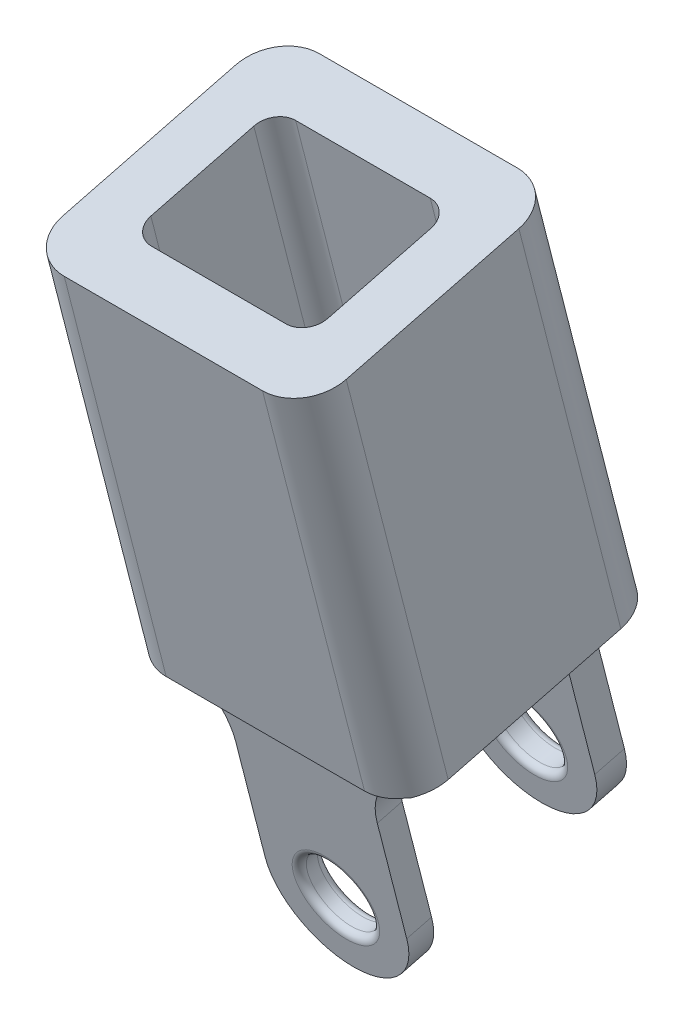
SolidWorks part; units mm, degrees
material "ABS"
ref_plane "Alzado" through (0, 0, 0) normal (0, 0, 1) x (1, 0, 0)
ref_plane "Planta" through (0, 0, 0) normal (0, 1, 0) x (1, 0, 0)
ref_plane "Vista lateral" through (0, 0, 0) normal (1, 0, 0) x (0, 0, -1)
sketch "Croquis1" plane through (0, 0, 0) normal (1, 0, 0) x (0, 0, -1)
  line L0 (268.1146, 425.6206) -> (162.8718, 393.6212) construction
  dimension "D1" = 110
sketch "Croquis2" plane through (0, 0, 0) normal (1, 0, 0) x (0, 0, -1)
  line L0 (116.0336, 334.5851) -> (134.0345, 339.2007)
  line L1 (134.0345, 339.2007) -> (141.2314, 311.1325)
  line L2 (141.2314, 311.1325) -> (123.2306, 306.5169)
  line L3 (123.2306, 306.5169) -> (116.0336, 334.5851)
  line L4 (124.8932, 306.9432) -> (129.4545, 289.1541)
  line L5 (129.4545, 289.1541) -> (144.8187, 293.0936)
  line L6 (144.8187, 293.0936) -> (140.2574, 310.8827)
  line L7 (126.9663, 306.1376) -> (129.9513, 294.496)
  line L8 (129.9513, 294.496) -> (141.4729, 297.4503)
  line L9 (141.4729, 297.4503) -> (138.4879, 309.0918)
  line L10 (138.4879, 309.0918) -> (126.9663, 306.1376)
extrude "Saliente-Extruir1" add sketch "Croquis2" along normal blind 20 contours L3 L2 L1 L0 | L5 L6 L2 L4 L10 L9 L8 L7 region at (0, 322.8588, -128.6325) region at (0, 308.6274, -132.6485)
sketch "Croquis3" plane through (20, 0, 0) normal (1, 0, 0) x (0, 0, -1)
  line L0 (124.8932, 306.9432) -> (140.2574, 310.8827)
  line L1 (124.8932, 306.9432) -> (129.4545, 289.1541)
  line L2 (129.4545, 289.1541) -> (144.8187, 293.0936)
  line L3 (144.8187, 293.0936) -> (140.2574, 310.8827)
extrude "Cortar-Extruir1" cut sketch "Croquis3" against normal blind 5
sketch "Croquis4" plane through (0, 0, 0) normal (-1, 0, 0) x (0, 0, 1)
  line L0 (-144.8187, 293.0936) -> (-140.2574, 310.8827)
  line L1 (-140.2574, 310.8827) -> (-124.8932, 306.9432)
  line L2 (-124.8932, 306.9432) -> (-129.4545, 289.1541)
  line L3 (-129.4545, 289.1541) -> (-144.8187, 293.0936)
extrude "Cortar-Extruir2" cut sketch "Croquis4" against normal blind 5
sketch "Croquis10" plane through (15, 0, 0) normal (1, 0, 0) x (0, 0, -1)
  line L0 (129.9513, 294.496) -> (131.2059, 289.6032)
  line L1 (129.4545, 289.1541) -> (144.8187, 293.0936) construction
  line L2 (129.9513, 294.496) -> (141.4729, 297.4503)
  line L3 (141.4729, 297.4503) -> (142.7274, 292.5574)
  line L4 (142.7274, 292.5574) -> (131.2059, 289.6032)
  line L5 (126.9663, 306.1376) -> (129.9513, 294.496) construction
extrude "Cortar-Extruir4" cut sketch "Croquis10" against normal through all
fillet "Redondeo2" radius 5 6 edges at (5, 289.3786, -130.3302) (15, 289.3786, -130.3302) (15, 292.8255, -143.7731) (5, 292.8255, -143.7731) (5, 308.913, -132.5753) (15, 308.913, -132.5753)
sketch "Croquis11" plane through (0, 49.4328, -192.788) normal (0, 0.2484, -0.9687) x (-1, 0, 0)
  circle A0 centre (-10, 252.9398) radius 2
  dimension "D1" = 4
extrude "Saliente-Extruir3" add sketch "Croquis11" along normal up to surface (11.8943 mm away) up to face at (10, 302.1256, -140.2741)
sketch "Croquis12" plane through (0, 286.0276, 73.3404) normal (0, 0.9687, 0.2484) x (1, 0, 0)
  line L0 (10, 214.0834) -> (10, 195.5003) construction
  line L1 (20, 214.0834) -> (0, 214.0834) construction
  line L2 (20, 195.5003) -> (0, 195.5003) construction
  line L4 (5.25, 210.0418) -> (14.75, 210.0418)
  line L5 (3.75, 208.5418) -> (3.75, 201.0418)
  line L6 (5.25, 199.5418) -> (14.75, 199.5418)
  line L7 (16.25, 208.5418) -> (16.25, 201.0418)
  line L8 (3.75, 210.0418) -> (16.25, 199.5418) construction
  line L9 (3.75, 199.5418) -> (16.25, 210.0418) construction
  arc A0 (14.75, 210.0418) -> (16.25, 208.5418) centre (14.75, 208.5418) cw
  arc A1 (14.75, 199.5418) -> (16.25, 201.0418) centre (14.75, 201.0418) ccw
  arc A2 (3.75, 201.0418) -> (5.25, 199.5418) centre (5.25, 201.0418) ccw
  arc A3 (5.25, 210.0418) -> (3.75, 208.5418) centre (5.25, 208.5418) ccw
  point P6 (10, 204.7918)
  dimension "D3" = 1.5
  dimension "D4" = 1.5
  dimension "D5" = 1.5
  dimension "D6" = 1.5
  dimension "D1" = 12.5
  dimension "D2" = 10.5
extrude "Cortar-Extruir5" cut sketch "Croquis12" against normal blind 20
fillet "Redondeo3" radius 3 4 edges at (0, 325.1666, -137.6329) (20, 325.1666, -137.6329) (20, 320.551, -119.6321) (0, 320.551, -119.6321)
fillet "Redondeo4" radius 1 2 edges at (10, 306.9432, -124.8932) (10, 310.8827, -140.2574)
fillet "Redondeo5" radius 2 2 edges at (10, 306.1376, -126.9663) (10, 309.0918, -138.4879)
sketch "Croquis13" plane through (0, 48.9838, -191.0367) normal (0, -0.2484, 0.9687) x (1, 0, 0)
  circle A0 centre (10, 252.9398) radius 2.5
  dimension "D1" = 5
extrude "Cortar-Extruir9" cut sketch "Croquis13" against normal through all contours A0
fillet "Redondeo6" radius 0.5 4 edges at (10, 295.5153, -144.1977) (10, 294.9791, -142.1065) (10, 296.8682, -129.3431) (10, 291.5758, -128.8336)
